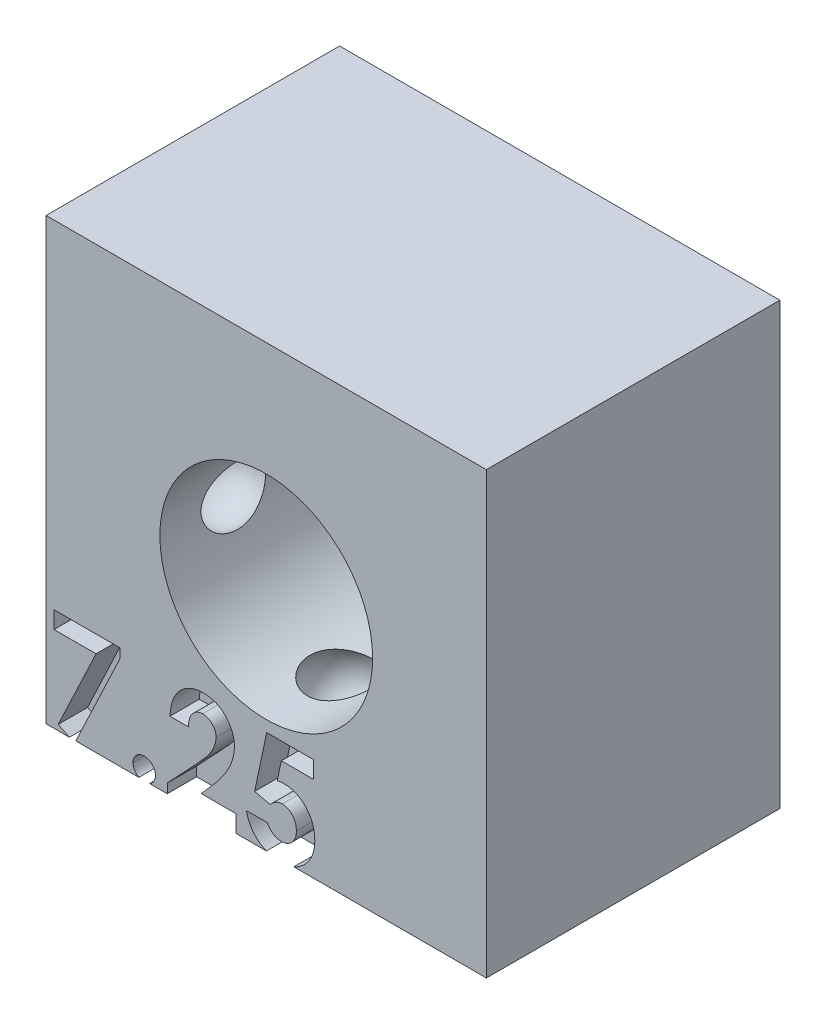
SolidWorks part; units mm, degrees
ref_plane "Front Plane" through (0, 0, 0) normal (0, 0, 1) x (1, 0, 0)
ref_plane "Top Plane" through (0, 0, 0) normal (0, 1, 0) x (1, 0, 0)
ref_plane "Right Plane" through (0, 0, 0) normal (1, 0, 0) x (0, 0, -1)
sketch "Sketch1" plane through (0, 0, 0) normal (0, 0, 1) x (1, 0, 0)
  line L1 (0, 0) -> (15, 0)
  line L2 (0, 0) -> (0, 15)
  line L3 (0, 15) -> (15, 15)
  line L4 (15, 0) -> (15, 15)
  circle A0 centre (7.5, 7.5) radius 3.625
  point P7 (7.5, 15)
  point P8 (15, 7.5)
  dimension "D2" = 7.25
  dimension "D1" = 15
extrude "Boss-Extrude1" add sketch "Sketch1" along normal blind 10
ref_axis "Axis1" through (7.5, 7.5, 10) along (0, 0, -1)
ref_plane "Plane1" through (7.5, 0, 0) normal (1, 0, 0) x (0, 0, -1)
sketch "Sketch2" plane through (7.5, 0, 0) normal (1, 0, 0) x (0, 0, -1)
  line L0 (-8.6, 11.125) -> (-6.4, 11.125) construction
  line L1 (0, 11.125) -> (-10, 11.125) construction
  line L2 (-10, 0) -> (-10, 15) construction
  line L3 (-8.75, 11.7187) -> (-6.25, 11.7187)
  circle A0 centre (-7.5, 11.7187) radius 1.25
  point P12 (-7.5, 11.7187)
  dimension "D1" = 2.5
  dimension "D2" = 2.2
  dimension "D3" = 2.5
revolve "Cut-Revolve1" cut sketch "Sketch2" angle 360 about L3 region at (7.5, 12.2492, 7.5) reverse direction yes
pattern_circular "CirPattern1" count 4 over 360 about axis through (7.5, 7.5, 10) along (0, 0, -1) of "Cut-Revolve1"
pattern_linear "LPattern1" count 2 spacing 5 along (0, 0, -1) of "CirPattern1"
sketch "Sketch3" [suppressed] plane through (0, 0, 10) normal (0, 0, 1) x (1, 0, 0)
  text T0 "7.55" font "Century Gothic" height 3.5
extrude "Cut-Extrude1" [suppressed] cut sketch "Sketch3" against normal blind 1
sketch "Sketch4" [suppressed] plane through (0, 0, 10) normal (0, 0, 1) x (1, 0, 0)
  text T0 "<b>7</b>"
extrude "Cut-Extrude2" [suppressed] cut sketch "Sketch4" against normal blind 1
sketch "Sketch5" [suppressed] plane through (0, 0, 10) normal (0, 0, 1) x (1, 0, 0)
  text T0 "<b>7.65</b>\r\n"
extrude "Cut-Extrude3" [suppressed] cut sketch "Sketch5" against normal blind 1
sketch "Sketch6" [suppressed] plane through (0, 0, 10) normal (0, 0, 1) x (1, 0, 0)
  text T0 "<b>7.45</b>"
extrude "Cut-Extrude4" [suppressed] cut sketch "Sketch6" against normal blind 1
sketch "Sketch7" plane through (0, 0, 10) normal (0, 0, 1) x (1, 0, 0)
  text T0 "<b>7.25</b>\r\n"
extrude "Cut-Extrude5" cut sketch "Sketch7" against normal blind 1
